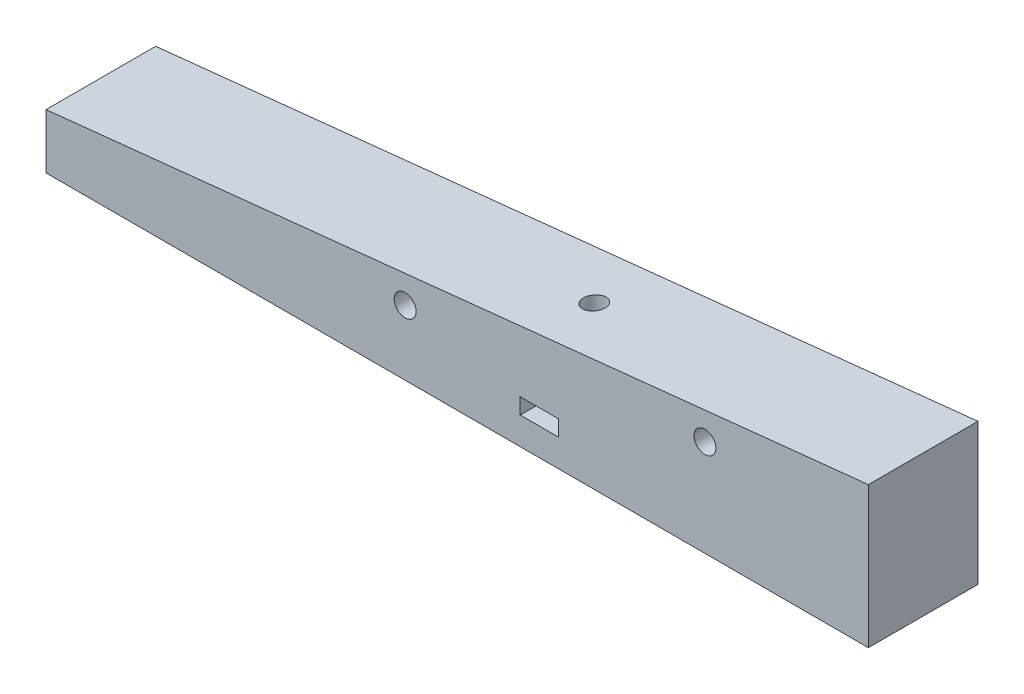
SolidWorks part; units mm, degrees
ref_plane "Front Plane" through (0, 0, 0) normal (0, 0, 1) x (1, 0, 0)
ref_plane "Top Plane" through (0, 0, 0) normal (0, 1, 0) x (1, 0, 0)
ref_plane "Right Plane" through (0, 0, 0) normal (1, 0, 0) x (0, 0, -1)
sketch "Sketch1" plane through (0, 0, 0) normal (0, 1, 0) x (1, 0, 0)
  line L1 (-75, -10) -> (75, -10)
  line L2 (-75, -10) -> (-75, 10)
  line L3 (-75, 10) -> (75, 10)
  line L4 (75, -10) -> (75, 10)
  line L5 (-75, -10) -> (75, 10) construction
  line L6 (-75, 10) -> (75, -10) construction
  point P0 (0, 0)
  dimension "D1" = 20
  dimension "D2" = 150
extrude "Boss-Extrude1" add sketch "Sketch1" along normal blind 10
sketch "Sketch2" plane through (0, 0, 0) normal (0, 0, 1) x (1, 0, 0)
  line L0 (-75, 10) -> (75, 10)
  line L1 (75, 10) -> (75, 25.7656)
  line L2 (75, 25.7656) -> (-75, 10)
  dimension "D1" = 6
extrude "Boss-Extrude2" add sketch "Sketch2" along normal mid plane 20
sketch "Sketch3" plane through (0, 0, 0) normal (0, -1, 0) x (1, 0, 0)
  line L0 (14.1711, 0) -> (-14.1711, 0) construction
  line L1 (0, -11) -> (0, 11) construction
  circle A0 centre (15, 0) radius 2
  dimension "D2" = 4
  dimension "D1" = 15
extrude "Cut-Extrude1" cut sketch "Sketch3" against normal through all both
sketch "Sketch4" plane through (0, 0, 10) normal (0, 0, 1) x (1, 0, 0)
  line L0 (0, -11) -> (0, 11) construction
  line L1 (11.5, 7.9) -> (18.5, 7.9)
  line L2 (11.5, 7.9) -> (11.5, 5)
  line L3 (11.5, 5) -> (18.5, 5)
  line L4 (18.5, 7.9) -> (18.5, 5)
  line L5 (11.5, 7.9) -> (18.5, 5) construction
  line L6 (11.5, 5) -> (18.5, 7.9) construction
  line L7 (11, 0) -> (-11, 0) construction
  line L8 (-10.0153, 16.8302) -> (-9.4927, 11.8576) construction
  line L9 (75, 25.7656) -> (-75, 10) construction
  line L10 (44.6638, 22.5772) -> (45.1865, 17.6046) construction
  circle A0 centre (-9.4927, 11.8576) radius 2
  circle A1 centre (45.1865, 17.6046) radius 2
  point P0 (15, 6.45)
  point P17 (0, 0)
  point P18 (0, 0)
  dimension "D9" = 4
  dimension "D10" = 4
  dimension "D1" = 15
  dimension "D2" = 7
  dimension "D3" = 2.9
  dimension "D4" = 5
  dimension "D5" = 90
  dimension "D6" = 90
  dimension "D7" = 5
  dimension "D8" = 5
extrude "Cut-Extrude2" cut sketch "Sketch4" against normal blind 13.8 contours L2 L3 L4 L1
extrude "Cut-Extrude3" cut sketch "Sketch4<3>" against normal through all both and the other way through all contours A0 | A1
sketch "Sketch4<3>" plane through (0, 0, 10) normal (0, 0, 1) x (1, 0, 0) same geometry as "Sketch4"
